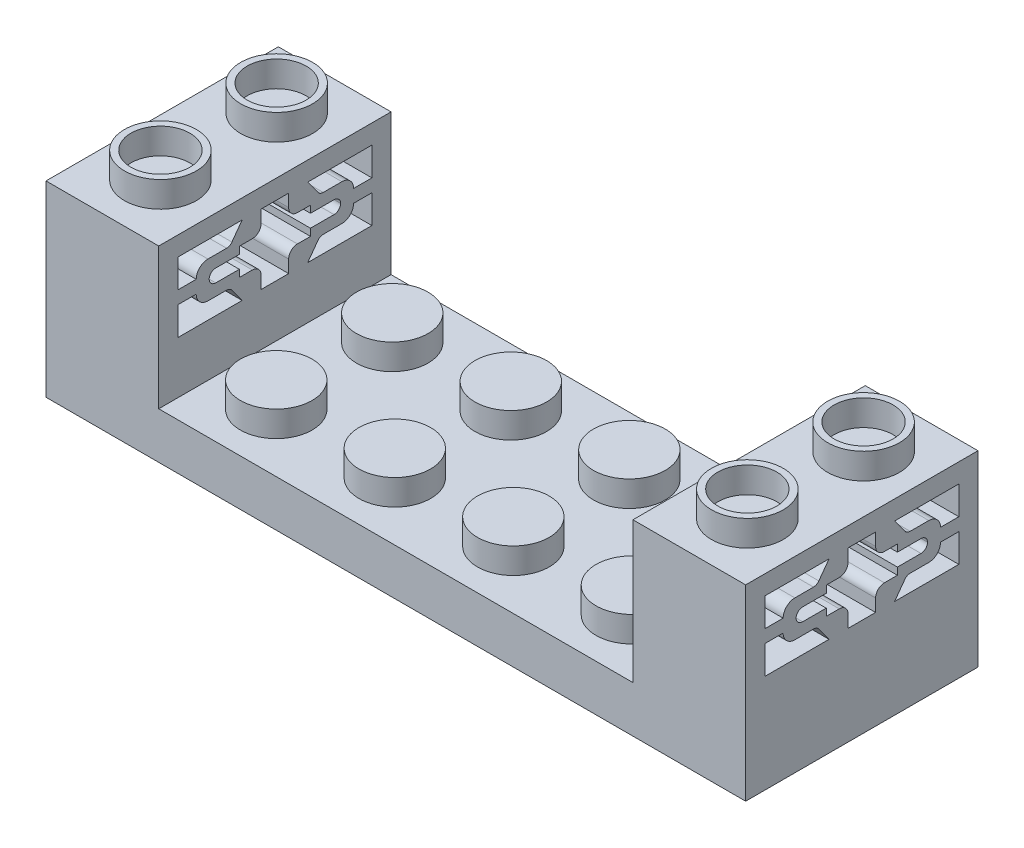
SolidWorks part; units mm, degrees
ref_plane "Front Plane" through (0, 0, 0) normal (0, 0, 1) x (1, 0, 0)
ref_plane "Top Plane" through (0, 0, 0) normal (0, 1, 0) x (1, 0, 0)
ref_plane "Right Plane" through (0, 0, 0) normal (1, 0, 0) x (0, 0, -1)
sketch "Sketch2" plane through (0, 0, 0) normal (0, 0, 1) x (1, 0, 0)
  line L1 (-23.895, 6.4) -> (23.895, 6.4)
  line L2 (-23.895, 6.4) -> (-23.895, -6.4)
  line L3 (-23.895, -6.4) -> (23.895, -6.4)
  line L4 (23.895, 6.4) -> (23.895, -6.4)
  line L5 (-23.895, 6.4) -> (23.895, -6.4) construction
  line L6 (-23.895, -6.4) -> (23.895, 6.4) construction
  point P0 (0, 0)
  dimension "D1" = 47.79
  dimension "D2" = 12.8
extrude "Boss-Extrude1" add sketch "Sketch2" against normal blind 15.87
sketch "Sketch3" plane through (0, 0, 0) normal (0, 0, 1) x (1, 0, 0)
  line L0 (-16.195, 6.4) -> (-16.195, -3.23)
  line L1 (23.895, 6.4) -> (-23.895, 6.4) construction
  line L2 (-16.195, -3.23) -> (16.195, -3.23)
  line L3 (16.195, -3.23) -> (16.195, 6.4)
  line L4 (-23.895, 6.4) -> (-23.895, -6.4) construction
  line L5 (23.895, -6.4) -> (23.895, 6.4) construction
  line L6 (-23.895, -6.4) -> (23.895, -6.4) construction
  dimension "D1" = 7.7
  dimension "D2" = 7.7
  dimension "D3" = 3.17
extrude "Cut-Extrude1" cut sketch "Sketch3" against normal through all and the other way through all
sketch "Sketch4" plane through (0, 6.4, 0) normal (0, 1, 0) x (1, 0, 0)
  line L0 (-23.895, 15.87) -> (-23.895, 0) construction
  line L1 (-20.045, 1.51) -> (-27.3582, 1.51) construction
  line L2 (-20.045, 14.36) -> (-27.3582, 14.36) construction
  line L3 (-27.3582, 7.935) -> (-12.7516, 7.935) construction
  line L4 (-16.195, 15.87) -> (-23.895, 15.87) construction
  line L5 (0, 20.0372) -> (0, -8.5068) construction
  line L8 (20.045, 1.51) -> (27.3582, 1.51) construction
  line L9 (27.3582, 7.935) -> (12.7516, 7.935) construction
  line L10 (20.045, 14.36) -> (27.3582, 14.36) construction
  circle A0 centre (-20.045, 11.905) radius 2.455
  circle A1 centre (-20.045, 3.965) radius 2.455
  circle A2 centre (-20.045, 11.905) radius 2.015
  circle A3 centre (-20.045, 3.965) radius 2.015
  circle A4 centre (20.045, 3.965) radius 2.455
  circle A5 centre (20.045, 3.965) radius 2.015
  circle A6 centre (20.045, 11.905) radius 2.455
  circle A7 centre (20.045, 11.905) radius 2.015
  dimension "D2" = 4.91
  dimension "D5" = 4.03
  dimension "D6" = 4.03
  dimension "D1" = 3.85
  dimension "D3" = 7.935
  dimension "D4" = 12.85
extrude "Boss-Extrude2" add sketch "Sketch4" along normal blind 1.76
sketch "Sketch5" plane through (0, -3.23, 0) normal (0, 1, 0) x (1, 0, 0)
  line L1 (16.195, 15.87) -> (-16.195, 15.87) construction
  line L3 (-16.195, 0) -> (-16.195, 15.87) construction
  line L4 (-15.4847, 7.94) -> (16.195, 7.94) construction
  line L5 (16.195, 0) -> (16.195, 15.87) construction
  line L6 (16.195, 0) -> (-16.195, 0) construction
  circle A0 centre (-12.1463, 11.9025) radius 2.45
  circle A1 centre (-4.0488, 11.9025) radius 2.45
  circle A2 centre (4.0488, 11.9025) radius 2.45
  circle A3 centre (12.1463, 11.9025) radius 2.45
  circle A4 centre (12.1463, 3.9775) radius 2.45
  circle A5 centre (4.0488, 3.9775) radius 2.45
  circle A6 centre (-4.0488, 3.9775) radius 2.45
  circle A7 centre (-12.1463, 3.9775) radius 2.45
  dimension "D1" = 4.9
  dimension "D2" = 3.9675
  dimension "D3" = 4.0488
  dimension "D5" = 8.0975
  dimension "D6" = 7.94
  dimension "D4" = 4
extrude "Boss-Extrude3" add sketch "Sketch5" along normal blind 1.75
sketch "Sketch6" plane through (0, -6.4, 0) normal (0, -1, 0) x (1, 0, 0)
  line L0 (-23.895, -15.87) -> (-23.895, 0) construction
  line L1 (-15.925, -1.6) -> (15.925, -1.6)
  line L2 (-15.925, -1.6) -> (-15.925, -14.27)
  line L3 (-15.925, -14.27) -> (15.925, -14.27)
  line L4 (15.925, -1.6) -> (15.925, -14.27)
  line L5 (-15.925, -1.6) -> (15.925, -14.27) construction
  line L6 (-15.925, -14.27) -> (15.925, -1.6) construction
  line L7 (23.895, -15.87) -> (23.895, 0) construction
  line L8 (-23.895, -15.87) -> (23.895, -15.87) construction
  line L9 (-23.895, 0) -> (23.895, 0) construction
  point P0 (0, -7.935)
  dimension "D1" = 7.97
  dimension "D2" = 7.97
  dimension "D3" = 1.6
  dimension "D4" = 1.6
extrude "Cut-Extrude3" cut sketch "Sketch6" against normal blind 1.6
sketch "Sketch7" plane through (0, -4.8, 0) normal (0, -1, 0) x (1, 0, 0)
  line L0 (-23.895, 0) -> (23.895, 0) construction
  line L1 (-23.895, -15.87) -> (-23.895, 0) construction
  line L3 (-15.925, -7.935) -> (15.925, -7.935) construction
  line L4 (-15.925, -1.6) -> (-15.925, -14.27) construction
  line L5 (15.925, -14.27) -> (15.925, -1.6) construction
  circle A0 centre (-12.145, -3.97) radius 1.65
  circle A1 centre (-4.045, -3.97) radius 1.65
  circle A2 centre (4.055, -3.97) radius 1.65
  circle A3 centre (12.155, -3.97) radius 1.65
  circle A4 centre (12.155, -11.9) radius 1.65
  circle A5 centre (4.055, -11.9) radius 1.65
  circle A6 centre (-4.045, -11.9) radius 1.65
  circle A7 centre (-12.145, -11.9) radius 1.65
  dimension "D1" = 3.3
  dimension "D2" = 3.97
  dimension "D5" = 8.1
  dimension "D3" = 11.75
  dimension "D4" = 4
extrude "Cut-Extrude4" cut sketch "Sketch7" against normal blind 1.85
sketch "Sketch8" plane through (0, -6.4, 0) normal (0, -1, 0) x (1, 0, 0)
  line L0 (23.895, -15.87) -> (23.895, 0) construction
  line L1 (17.685, -1.52) -> (22.375, -1.52)
  line L2 (17.685, -1.52) -> (17.685, -14.35)
  line L3 (17.685, -14.35) -> (22.375, -14.35)
  line L4 (22.375, -1.52) -> (22.375, -14.35)
  line L5 (17.685, -1.52) -> (22.375, -14.35) construction
  line L6 (17.685, -14.35) -> (22.375, -1.52) construction
  line L7 (15.925, -14.27) -> (15.925, -1.6) construction
  line L8 (-23.895, 0) -> (23.895, 0) construction
  line L9 (-23.895, -15.87) -> (23.895, -15.87) construction
  line L10 (0, 4.4591) -> (0, -22.987) construction
  line L11 (-17.685, -14.35) -> (-22.375, -1.52) construction
  line L12 (-17.685, -1.52) -> (-22.375, -14.35) construction
  line L13 (-22.375, -1.52) -> (-22.375, -14.35)
  line L14 (-17.685, -14.35) -> (-22.375, -14.35)
  line L15 (-17.685, -1.52) -> (-17.685, -14.35)
  line L16 (-17.685, -1.52) -> (-22.375, -1.52)
  point P0 (20.03, -7.935)
  point P20 (-20.03, -7.935)
  dimension "D1" = 1.52
  dimension "D2" = 1.76
  dimension "D3" = 1.52
  dimension "D4" = 1.52
extrude "Cut-Extrude6" cut sketch "Sketch8" against normal blind 5.52
sketch "Sketch9" plane through (0, -4.8, 0) normal (0, -1, 0) x (1, 0, 0)
  line L0 (-15.925, -1.6) -> (-15.925, -14.27) construction
  line L1 (-15.925, -1.6) -> (-15.925, -14.27) construction
  line L2 (-23.895, 0) -> (23.895, 0) construction
  line L3 (15.925, -14.27) -> (15.925, -1.6) construction
  line L4 (15.925, -14.27) -> (15.925, -1.6) construction
  circle A0 centre (-7.9625, -7.935) radius 3.23
  circle A1 centre (0, -7.935) radius 3.23
  circle A2 centre (7.9625, -7.935) radius 3.23
  arc A3 (-15.925, -11.165) -> (-15.925, -4.705) centre (-15.925, -7.935) ccw
  circle A4 centre (-7.9625, -7.935) radius 2.83
  circle A5 centre (0, -7.935) radius 2.83
  circle A6 centre (7.9625, -7.935) radius 2.83
  arc A7 (-15.925, -10.765) -> (-15.925, -5.105) centre (-15.925, -7.935) ccw
  arc A8 (15.925, -11.165) -> (15.925, -4.705) centre (15.925, -7.935) cw
  arc A9 (15.925, -10.765) -> (15.925, -5.105) centre (15.925, -7.935) cw
  line M9 (15.925, -14.27) -> (15.925, -1.6)
  line M11 (-15.925, -1.6) -> (-15.925, -14.27)
  dimension "D1" = 6.46
  dimension "D2" = 7.935
  dimension "D5" = 7.9625
  dimension "D6" = 3.23
  dimension "D7" = 5.66
  dimension "D9" = 7.9625
  dimension "D10" = 2.83
  dimension "D11" = 3.23
  dimension "D12" = 2.83
  dimension "D3" = 7.9625
  dimension "D4" = 3
  dimension "D8" = 3
extrude "Boss-Extrude5" add sketch "Sketch9" along normal offset from surface (1.4 mm away) 0.2 contours A7 A3 M11 | A0 A4 | A1 A5 | A2 A6 | A9 A8 M9 region at (-11.1011, -4.8, -7.935) region at (-3.1386, -4.8, -7.935) region at (4.8239, -4.8, -7.935) region at (-15.8528, -4.8, -10.965) region at (12.7672, -4.8, -7.935) up to face at (20.03, -6.4, -7.935)
sketch "Sketch10" plane through (0, -0.88, 0) normal (0, -1, 0) x (1, 0, 0)
  line L1 (-23.895, 0) -> (23.895, 0) construction
  line L2 (-23.895, -15.87) -> (-23.895, 0) construction
  circle A0 centre (-19.91, -7.935) radius 1.48
  circle A1 centre (-19.91, -7.935) radius 1.015
  dimension "D1" = 2.96
  dimension "D2" = 7.935
  dimension "D4" = 2.03
  dimension "D3" = 3.985
extrude "Boss-Extrude6" add sketch "Sketch10" along normal up to surface (5.32 mm away) up to face at (-14.41, -6.2, -7.935)
sketch "Sketch11" plane through (0, -0.88, 0) normal (0, -1, 0) x (1, 0, 0)
  line L0 (23.895, -15.87) -> (23.895, 0) construction
  line L1 (-23.895, 0) -> (23.895, 0) construction
  circle A0 centre (19.91, -7.935) radius 1.48
  circle A3 centre (19.91, -7.935) radius 1.015
  dimension "D1" = 3.985
  dimension "D2" = 2.96
  dimension "D3" = 7.935
  dimension "D4" = 2.03
extrude "Boss-Extrude7" add sketch "Sketch11" along normal up to surface (5.32 mm away) up to face at (14.41, -6.2, -7.935)
sketch "Sketch12" plane through (23.895, 0, 0) normal (1, 0, 0) x (0, 0, -1)
  line L0 (10.1741, 5.09) -> (14.56, 5.09)
  line L1 (14.56, 5.09) -> (14.56, 3.15)
  line L2 (14.56, 3.15) -> (13.31, 3.15)
  line L3 (13.31, 3.15) -> (13.31, 3.95)
  line L4 (13.31, 3.95) -> (11.008, 3.95)
  line L5 (11.008, 3.95) -> (10.1741, 5.09)
  line L6 (15.87, -6.4) -> (15.87, 6.4) construction
  line L7 (15.87, 6.4) -> (0, 6.4) construction
  line L8 (6.995, 5.09) -> (8.875, 5.09)
  line L9 (8.875, 5.09) -> (8.875, 3.635)
  line L10 (8.875, 3.635) -> (10.365, 3.635)
  line L11 (10.365, 3.635) -> (10.365, 3.15)
  line L12 (10.365, 3.15) -> (12.425, 3.15)
  line L16 (0, -6.4) -> (0, 6.4) construction
  line L17 (15.87, -6.4) -> (0, -6.4) construction
  line L18 (5.6959, 0.33) -> (1.31, 0.33)
  line L20 (10.365, 2.27) -> (12.425, 2.27)
  line L21 (10.365, 1.785) -> (10.365, 2.27)
  line L22 (8.875, 1.785) -> (10.365, 1.785)
  line L23 (8.875, 0.33) -> (8.875, 1.785)
  line L24 (6.995, 0.33) -> (8.875, 0.33)
  line L25 (11.008, 1.47) -> (10.1741, 0.33)
  line L26 (13.31, 1.47) -> (11.008, 1.47)
  line L27 (13.31, 2.27) -> (13.31, 1.47)
  line L28 (14.56, 2.27) -> (13.31, 2.27)
  line L29 (14.56, 0.33) -> (14.56, 2.27)
  line L30 (10.1741, 0.33) -> (14.56, 0.33)
  line L31 (1.31, 0.33) -> (1.31, 2.27)
  line L32 (1.31, 2.27) -> (2.56, 2.27)
  line L33 (2.56, 2.27) -> (2.56, 1.47)
  line L34 (2.56, 1.47) -> (4.862, 1.47)
  line L35 (4.862, 1.47) -> (5.6959, 0.33)
  line L36 (6.995, 0.33) -> (6.995, 1.785)
  line L37 (6.995, 1.785) -> (5.505, 1.785)
  line L38 (5.505, 1.785) -> (5.505, 2.27)
  line L39 (5.505, 2.27) -> (3.445, 2.27)
  line L42 (5.505, 3.15) -> (3.445, 3.15)
  line L43 (5.505, 3.635) -> (5.505, 3.15)
  line L44 (6.995, 3.635) -> (5.505, 3.635)
  line L45 (6.995, 5.09) -> (6.995, 3.635)
  line L46 (4.862, 3.95) -> (5.6959, 5.09)
  line L47 (2.56, 3.95) -> (4.862, 3.95)
  line L48 (2.56, 3.15) -> (2.56, 3.95)
  line L49 (1.31, 3.15) -> (2.56, 3.15)
  line L50 (1.31, 5.09) -> (1.31, 3.15)
  line L51 (5.6959, 5.09) -> (1.31, 5.09)
  line L52 (12.425, 3.15) -> (12.425, 2.27)
  line L53 (3.445, 3.15) -> (3.445, 2.27)
  point P45 (7.935, 2.71)
  point P57 (13.935, 2.27)
  dimension "D1" = 1.31
  dimension "D2" = 1.31
  dimension "D3" = 1.25
  dimension "D4" = 1.94
  dimension "D5" = 1.14
  dimension "D6" = 2.302
  dimension "D7" = 126.187
  dimension "D8" = 1.88
  dimension "D9" = 1.49
  dimension "D10" = 1.94
  dimension "D11" = 1.14
  dimension "D12" = 2.06
  dimension "D13" = 2.06
  dimension "D14" = 0.88
  dimension "D15" = 6.73
  dimension "D16" = 6.73
  dimension "D17" = 1.31
  dimension "D18" = 1.31
  dimension "D19" = 1.31
  dimension "D20" = 1.31
  dimension "D21" = 1.14
  dimension "D22" = 2.302
  dimension "D23" = 126.187
  dimension "D24" = 1.25
  dimension "D25" = 1.25
  dimension "D26" = 1.25
  dimension "D27" = 1.14
  dimension "D28" = 1.94
  dimension "D29" = 1.94
  dimension "D30" = 126.187
  dimension "D31" = 2.302
  dimension "D32" = 2.302
  dimension "D33" = 126.187
  dimension "D34" = 0.485
  dimension "D35" = 1.88
  dimension "D36" = 1.49
  dimension "D37" = 6.995
  dimension "D39" = 6.995
  dimension "D40" = 0.485
  dimension "D41" = 0.88
  dimension "D42" = 1.49
  dimension "D43" = 0.485
  dimension "D44" = 0.485
  dimension "D45" = 1.455
  dimension "D46" = 1.455
extrude "Cut-Extrude7" cut sketch "Sketch12" against normal through all
fillet "Fillet1" radius 0.6 8 edges at (-20.045, 3.635, -8.875) (-20.045, 3.635, -6.995) (-20.045, 1.785, -6.995) (20.045, 1.785, -6.995) (20.045, 3.635, -6.995) (20.045, 1.785, -8.875) (20.045, 3.635, -8.875) (-20.045, 1.785, -8.875)
fillet "Fillet2" radius 0.8 8 edges at (20.045, 3.95, -2.56) (20.045, 1.47, -2.56) (20.045, 1.47, -13.31) (20.045, 3.95, -13.31) (-20.045, 1.47, -2.56) (-20.045, 3.95, -2.56) (-20.045, 1.47, -13.31) (-20.045, 3.95, -13.31)
fillet "Fillet3" radius 0.45 4 edges at (-20.045, 2.27, -12.425) (-20.045, 3.15, -3.445) (-20.045, 2.27, -3.445) (-20.045, 3.15, -12.425)
fillet "Fillet4" radius 0.45 4 edges at (20.045, 3.15, -3.445) (20.045, 3.15, -12.425) (20.045, 2.27, -12.425) (20.045, 2.27, -3.445)
fillet "Fillet5" radius 0.45 8 edges at (-20.045, 1.47, -11.008) (-20.045, 3.95, -11.008) (-20.045, 1.47, -4.862) (-20.045, 3.95, -4.862) (20.045, 1.47, -11.008) (20.045, 1.47, -4.862) (20.045, 3.95, -4.862) (20.045, 3.95, -11.008)
